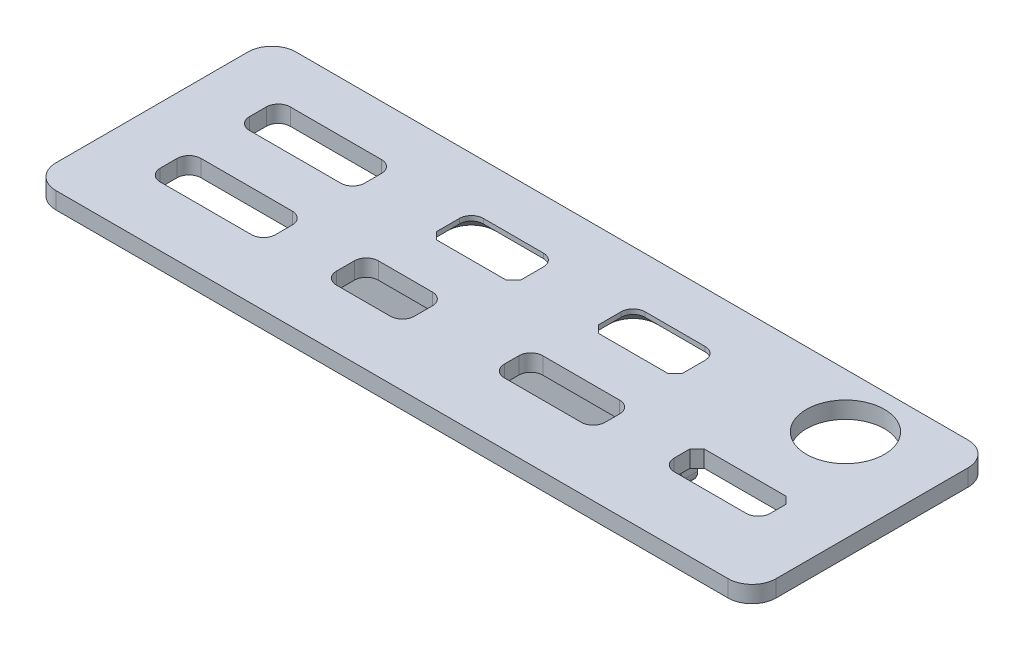
SolidWorks part; units mm, degrees
ref_plane "前视基准面" through (0, 0, 0) normal (0, 0, 1) x (1, 0, 0)
ref_plane "上视基准面" through (0, 0, 0) normal (0, 1, 0) x (1, 0, 0)
ref_plane "右视基准面" through (0, 0, 0) normal (1, 0, 0) x (0, 0, -1)
sketch "草图1" plane through (0, 0, 0) normal (0, 1, 0) x (1, 0, 0)
  line L1 (-30, 10) -> (30, 10)
  line L2 (-30, 10) -> (-30, -10)
  line L3 (-30, -10) -> (30, -10)
  line L4 (30, 10) -> (30, -10)
  line L5 (-30, 10) -> (30, -10) construction
  line L6 (-30, -10) -> (30, 10) construction
  point P0 (0, 0)
  dimension "D1" = 60
  dimension "D2" = 20
extrude "凸台-拉伸1" add sketch "草图1" along normal blind 1.4
fillet "圆角1" radius 2 4 edges at (30, 0.7, 10) (30, 0.7, -10) (-30, 0.7, 10) (-30, 0.7, -10)
sketch "草图4" plane through (0, 1.4, 0) normal (0, 1, 0) x (1, 0, 0)
  line L0 (-30, 8) -> (-30, -8) construction
  line L1 (-25.2717, 5.8) -> (-15.6717, 5.8)
  line L2 (-25.2717, 5.8) -> (-25.2717, 2.4)
  line L3 (-25.2717, 2.4) -> (-15.6717, 2.4)
  line L4 (-15.6717, 5.8) -> (-15.6717, 2.4)
  line L5 (-9.1829, 5.8) -> (-2.1829, 5.8)
  line L6 (-9.1829, 5.8) -> (-9.1829, 2.3)
  line L7 (-9.1829, 2.3) -> (-2.1829, 2.3)
  line L8 (-2.1829, 5.8) -> (-2.1829, 2.3)
  line L9 (4.2885, 5.8) -> (11.2885, 5.8)
  line L10 (4.2885, 5.8) -> (4.2885, 2.3)
  line L11 (4.2885, 2.3) -> (11.2885, 2.3)
  line L12 (11.2885, 5.8) -> (11.2885, 2.3)
  line L13 (17.05, -1.6348) -> (25.05, -1.6348)
  line L14 (17.05, -1.6348) -> (17.05, -4.5348)
  line L15 (17.05, -4.5348) -> (25.05, -4.5348)
  line L16 (25.05, -1.6348) -> (25.05, -4.5348)
  line L17 (3.2, -1.6348) -> (11.6, -1.6348)
  line L18 (3.2, -1.6348) -> (3.2, -4.8348)
  line L19 (3.2, -4.8348) -> (11.6, -4.8348)
  line L20 (11.6, -1.6348) -> (11.6, -4.8348)
  line L21 (-10.5, -1.6348) -> (-4, -1.6348)
  line L22 (-10.5, -1.6348) -> (-10.5, -5.1348)
  line L23 (-10.5, -5.1348) -> (-4, -5.1348)
  line L24 (-4, -1.6348) -> (-4, -5.1348)
  line L25 (-25.2717, -1.6348) -> (-15.6717, -1.6348)
  line L26 (-25.2717, -1.6348) -> (-25.2717, -5.0348)
  line L27 (-25.2717, -5.0348) -> (-15.6717, -5.0348)
  line L28 (-15.6717, -1.6348) -> (-15.6717, -5.0348)
  line L29 (28, 10) -> (-28, 10) construction
  line L30 (-28, -10) -> (28, -10) construction
  line L31 (30, -8) -> (30, 8) construction
  circle A0 centre (22.2985, 5.4832) radius 3.25
  dimension "D21" = 6.5
  dimension "D1" = 3.5
  dimension "D2" = 6.5
  dimension "D3" = 8.4
  dimension "D4" = 3.2
  dimension "D5" = 9.6
  dimension "D6" = 3.4
  dimension "D7" = 7
  dimension "D8" = 8
  dimension "D9" = 2.9
  dimension "D10" = 4.7283
  dimension "D11" = 7.6
  dimension "D12" = 4.9652
  dimension "D13" = 19.5
  dimension "D14" = 33.2
  dimension "D15" = 4.95
  dimension "D16" = 7
  dimension "D17" = 20.8171
  dimension "D18" = 34.2885
  dimension "D19" = 7.7015
  dimension "D20" = 4.5168
  dimension "D22" = 3.5
extrude "切除-拉伸1" cut sketch "草图4" against normal up to next
fillet "圆角2" radius 1 22 edges at (-25.2717, 0.7, -2.4) (-25.2717, 0.7, -5.8) (-15.6717, 0.7, -2.4) (-15.6717, 0.7, -5.8) (-2.1829, 0.7, -5.8) (-9.1829, 0.7, -5.8) (4.2885, 0.7, -5.8) (11.2885, 0.7, -5.8) (25.05, 0.7, 4.5348) (17.05, 0.7, 4.5348) (11.6, 0.7, 4.8348) (11.6, 0.7, 1.6348) (3.2, 0.7, 1.6348) (3.2, 0.7, 4.8348) (-4, 0.7, 5.1348) (-4, 0.7, 1.6348) (-10.5, 0.7, 1.6348) (-10.5, 0.7, 5.1348) (-15.6717, 0.7, 5.0348) (-15.6717, 0.7, 1.6348) (-25.2717, 0.7, 1.6348) (-25.2717, 0.7, 5.0348)
chamfer "倒角1" distance 0.6 angle 45 6 edges at (-9.1829, 0.7, -2.3) (-2.1829, 0.7, -2.3) (4.2885, 0.7, -2.3) (11.2885, 0.7, -2.3) (17.05, 0.7, 1.6348) (25.05, 0.7, 1.6348)
sketch "草图5" plane through (0, 0, 0) normal (0, -1, 0) x (1, 0, 0)
  line L0 (-30, -8) -> (-30, 8) construction
  line L1 (-13.9089, -4.8832) -> (-12.4089, -4.8832)
  line L2 (-13.9089, -4.8832) -> (-13.9089, 3.1168)
  line L3 (-13.9089, 3.1168) -> (-12.4089, 3.1168)
  line L4 (-12.4089, -4.8832) -> (-12.4089, 3.1168)
  line L5 (13.0911, -4.8832) -> (14.5911, -4.8832)
  line L6 (13.0911, -4.8832) -> (13.0911, 3.1168)
  line L7 (13.0911, 3.1168) -> (14.5911, 3.1168)
  line L8 (14.5911, -4.8832) -> (14.5911, 3.1168)
  line L9 (28, -10) -> (-28, -10) construction
  line L10 (30, 8) -> (30, -8) construction
  dimension "D1" = 1.5
  dimension "D2" = 8
  dimension "D3" = 1.5
  dimension "D4" = 8
  dimension "D5" = 16.0911
  dimension "D6" = 5.1168
  dimension "D7" = 5.1168
  dimension "D8" = 15.4089
extrude "凸台-拉伸2" add sketch "草图5" along normal blind 0.95
sketch "草图6" plane through (0, 0, 0) normal (0, -1, 0) x (1, 0, 0)
  line L0 (-13.9089, 3.1168) -> (-13.9089, -4.8832) construction
  line L1 (-13.9089, 0.5168) -> (14.5911, 0.5168)
  line L2 (-13.9089, 0.5168) -> (-13.9089, -0.8832)
  line L3 (-13.9089, -0.8832) -> (14.5911, -0.8832)
  line L4 (14.5911, 0.5168) -> (14.5911, -0.8832)
extrude "凸台-拉伸3" add sketch "草图6" along normal blind 4
fillet "圆角3" radius 1 2 edges at (14.5911, -4, -0.1832) (-13.9089, -4, -0.1832)
chamfer "倒角2" distance 1 angle 45 4 edges at (13.8411, -0.95, -4.8832) (-13.1589, -0.95, -4.8832) (13.8411, -0.95, 3.1168) (-13.1589, -0.95, 3.1168)
chamfer "倒角4" distance 1 angle 45 16 edges at (11.2885, 0, -3.85) (10.9956, 0, -5.5071) (7.7885, 0, -5.8) (4.5814, 0, -5.5071) (10.9885, 0, -2.6) (4.2885, 0, -3.85) (4.5885, 0, -2.6) (7.7885, 0, -2.3) (-9.1829, 0, -3.85) (-2.1829, 0, -3.85) (-8.89, 0, -5.5071) (-2.4758, 0, -5.5071) (-5.6829, 0, -5.8) (-2.4829, 0, -2.6) (-8.8829, 0, -2.6) (-5.6829, 0, -2.3)
